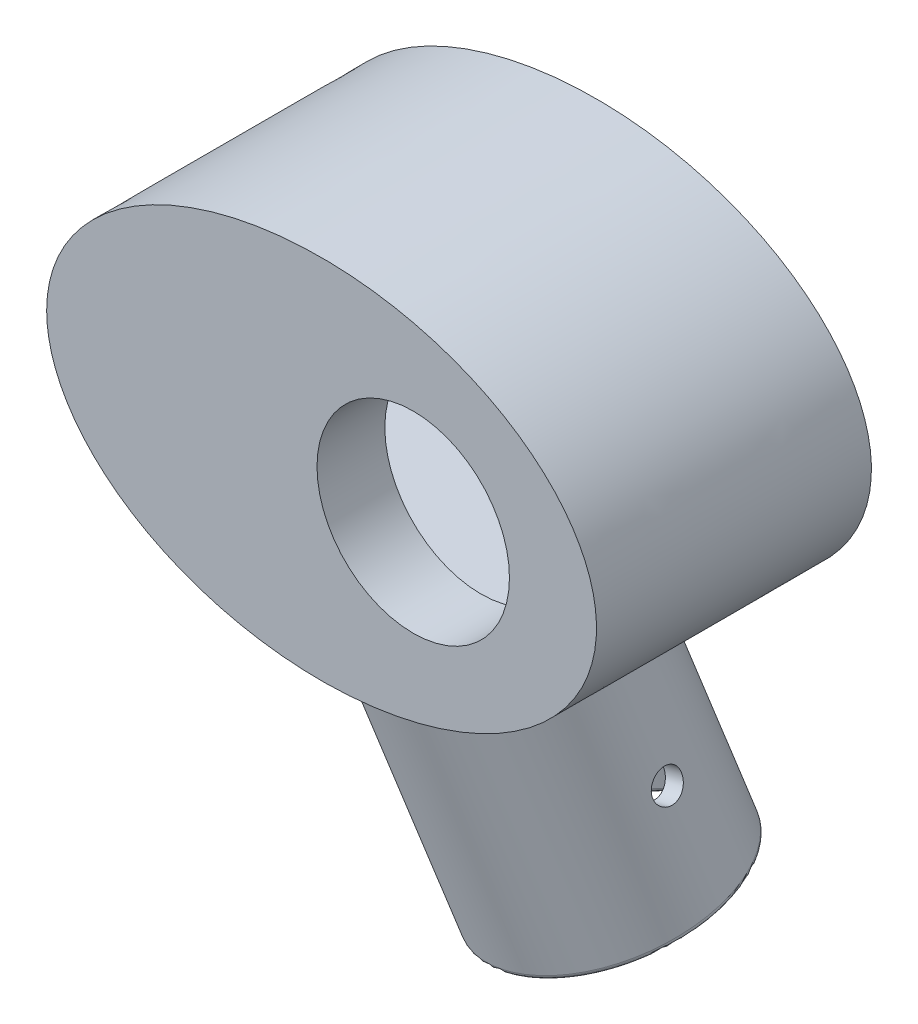
SolidWorks part; units mm, degrees
ref_plane "Front Plane" through (0, 0, 0) normal (0, 0, 1) x (1, 0, 0)
ref_plane "Top Plane" through (0, 0, 0) normal (0, 1, 0) x (1, 0, 0)
ref_plane "Right Plane" through (0, 0, 0) normal (1, 0, 0) x (0, 0, -1)
sketch "Sketch2" plane through (0, 0, 0) normal (0, 0, 1) x (1, 0, 0)
  line L102 (-3.3983, 10.2) -> (7.0395, 10.2) construction
  line L103 (7.0395, 10.2) -> (29.1, 10.2) construction
  line L104 (30.1, 9.2) -> (30.1, 0.75) construction
  line L105 (31.7, 0.75) -> (30.1, 0.75) construction
  line L106 (31.7, 0.75) -> (35.9, 0.75) construction
  line L107 (35.9, 0.75) -> (35.9, -0.75) construction
  line L108 (35.9, -0.75) -> (30.1, -0.75) construction
  line L109 (30.1, -0.75) -> (30.1, -9.2) construction
  line L110 (29.1, -10.2) -> (7.0395, -10.2) construction
  line L111 (7.0395, -10.2) -> (-3.3983, -10.2) construction
  line L112 (-3.3983, -10.2) -> (-9.1, -10.2) construction
  line L113 (-11.7, -0.75) -> (-10.1, -0.75) construction
  line L114 (-11.7, -0.75) -> (-15.9, -0.75) construction
  line L115 (-15.9, -0.75) -> (-15.9, 0.75) construction
  line L116 (-15.9, 0.75) -> (-11.7, 0.75) construction
  line L117 (-10.1, 0.75) -> (-11.7, 0.75) construction
  line L118 (-10.1, -9.2) -> (-10.1, -0.75) construction
  line L119 (-10.1, 0.75) -> (-10.1, 9.2) construction
  line L120 (-9.1, 10.2) -> (-3.3983, 10.2) construction
  line L121 (-3.3983, 10.6) -> (7.0395, 10.6)
  line L122 (7.0395, 10.6) -> (29.1, 10.6)
  line L123 (30.5, 9.2) -> (30.5, 1.15)
  line L124 (31.7, 1.15) -> (30.5, 1.15)
  line L125 (31.7, 1.15) -> (36.3, 1.15)
  line L126 (36.3, 1.15) -> (36.3, -1.15)
  line L127 (36.3, -1.15) -> (30.5, -1.15)
  line L128 (30.5, -1.15) -> (30.5, -9.2)
  line L129 (29.1, -10.6) -> (7.0395, -10.6)
  line L130 (7.0395, -10.6) -> (-3.3983, -10.6)
  line L131 (-3.3983, -10.6) -> (-9.1, -10.6)
  line L132 (-10.5, -9.2) -> (-10.5, -1.15)
  line L133 (-11.7, -1.15) -> (-10.5, -1.15)
  line L134 (-11.7, -1.15) -> (-16.3, -1.15)
  line L135 (-16.3, -1.15) -> (-16.3, 1.15)
  line L136 (-16.3, 1.15) -> (-11.7, 1.15)
  line L137 (-10.5, 1.15) -> (-11.7, 1.15)
  line L138 (-10.5, 1.15) -> (-10.5, 9.2)
  line L139 (-9.1, 10.6) -> (-3.3983, 10.6)
  arc A20 (30.1, 9.2) -> (29.1, 10.2) centre (29.1, 9.2) ccw construction
  arc A21 (29.1, -10.2) -> (30.1, -9.2) centre (29.1, -9.2) ccw construction
  arc A22 (-10.1, -9.2) -> (-9.1, -10.2) centre (-9.1, -9.2) ccw construction
  arc A23 (-9.1, 10.2) -> (-10.1, 9.2) centre (-9.1, 9.2) ccw construction
  arc A24 (30.5, 9.2) -> (29.1, 10.6) centre (29.1, 9.2) ccw
  arc A25 (29.1, -10.6) -> (30.5, -9.2) centre (29.1, -9.2) ccw
  arc A26 (-10.5, -9.2) -> (-9.1, -10.6) centre (-9.1, -9.2) ccw
  arc A27 (-9.1, 10.6) -> (-10.5, 9.2) centre (-9.1, 9.2) ccw
  ellipse E0 centre (10, 0) end of major axis (40, 0) minor radius 20
  dimension "D2" = 60
  dimension "D3" = 40
  dimension "D4" = 10
  dimension "D1" = 0.4
extrude "Boss-Extrude1" add sketch "Sketch2" along normal blind 30 contours E0 region at (-19.2789, -0.0201, 0)
sketch "Sketch3" plane through (0, 0, 0) normal (0, 0, -1) x (-1, 0, 0)
  arc A0 (-36.8729, -5.875) -> (-36.8729, -4.125) centre (-34.8, -5) ccw construction
  arc A1 (-36.8729, 4.125) -> (-36.8729, 5.875) centre (-34.8, 5) ccw construction
  arc A2 (16.8729, 5.875) -> (16.8729, 4.125) centre (14.8, 5) ccw construction
  arc A3 (16.8729, -4.125) -> (16.8729, -5.875) centre (14.8, -5) ccw construction
  arc A4 (-36.8729, -5.875) -> (-36.8729, -4.125) centre (-34.8, -5) ccw construction
  arc A5 (-36.8729, 4.125) -> (-36.8729, 5.875) centre (-34.8, 5) ccw construction
  arc A6 (16.8729, 5.875) -> (16.8729, 4.125) centre (14.8, 5) ccw construction
  arc A7 (16.8729, -4.125) -> (16.8729, -5.875) centre (14.8, -5) ccw construction
  arc A8 (16.8729, -5.875) -> (16.8729, -4.125) centre (14.8, -5) ccw construction
  arc A9 (16.8729, 4.125) -> (16.8729, 5.875) centre (14.8, 5) ccw construction
  arc A10 (-36.8729, 5.875) -> (-36.8729, 4.125) centre (-34.8, 5) ccw construction
  arc A11 (-36.8729, -4.125) -> (-36.8729, -5.875) centre (-34.8, -5) ccw construction
  arc A12 (-35.9516, -5.4861) -> (-35.9516, -4.5139) centre (-34.8, -5) ccw
  arc A13 (-35.9516, -4.5139) -> (-35.9516, -5.4861) centre (-34.8, -5) ccw
  arc A14 (-35.9516, 4.5139) -> (-35.9516, 5.4861) centre (-34.8, 5) ccw
  arc A15 (-35.9516, 5.4861) -> (-35.9516, 4.5139) centre (-34.8, 5) ccw
  arc A16 (15.9516, 5.4861) -> (15.9516, 4.5139) centre (14.8, 5) ccw
  arc A17 (15.9516, 4.5139) -> (15.9516, 5.4861) centre (14.8, 5) ccw
  arc A18 (15.9516, -4.5139) -> (15.9516, -5.4861) centre (14.8, -5) ccw
  arc A19 (15.9516, -5.4861) -> (15.9516, -4.5139) centre (14.8, -5) ccw
  dimension "D1" = 1.25
extrude "Cut-Extrude1" cut sketch "Sketch3" against normal blind 3
ref_plane "Plane3" through (10, 0, 0) normal (1, 0, 0) x (0, 0, -1)
sketch "Sketch16" [suppressed] plane through (10, 0, 0) normal (1, 0, 0) x (0, 0, -1)
  line L0 (0, 0) -> (50000, 0) construction
ref_plane "Plane6" [suppressed] through (9.648, 1.8427, 0) normal (-0.9822, -0.1876, 0) x (0, 0, -1)
sketch "Sketch6" plane through (11.1721, -6.137, 0) normal (-0.9822, -0.1876, 0) x (-0.1876, 0.9822, 0)
  line L1 (26.6831, 0) -> (-14.1873, 0) construction
  line L3 (-14.1873, -30) -> (26.6831, -30) construction
  line L7 (26.6831, -15) -> (51.6831, -15)
  line L8 (26.6831, 0) -> (-14.1873, 0) construction
  line L9 (-14.1873, -30) -> (26.6831, -30) construction
  line L10 (26.6831, 0) -> (26.6831, -30) construction
  dimension "D1" = 25
ref_plane "Plane1" through (1.4762, 44.6285, 15) normal (-0.1876, 0.9822, 0) x (0.9822, 0.1876, 0)
sketch "Sketch7" plane through (1.4762, 44.6285, 15) normal (-0.1876, 0.9822, 0) x (0.9822, 0.1876, 0)
  circle A0 centre (0, 0) radius 10.35
  circle A1 centre (0, 0) radius 12.35
  point P12 (0, 0)
  dimension "D1" = 20.7
  dimension "D2" = 2
extrude "Boss-Extrude2" [suppressed] add sketch "Sketch7" against normal up to body
sketch "Sketch8" plane through (0, 0, 30) normal (0, 0, 1) x (1, 0, 0)
  line L0 (10, 0) -> (10, -3.4904) construction
  ellipse E0 centre (10, 0) end of major axis (40, 0) minor radius 20 construction
  ellipse E1 centre (10, 0) end of major axis (40, 0) minor radius 20
extrude "Boss-Extrude4" add sketch "Sketch8" against normal up to surface (7.4 mm away)
sketch "Sketch12" [suppressed] plane through (10, -10, 0) normal (-1, 0, 0) x (0, 1, 0)
  line L6 (30, -30) -> (30, 0) construction
  line L7 (30, -15) -> (52.3116, -15) construction
  circle A0 centre (41.1558, -15) radius 1.7
  ellipse E0 centre (54.6285, -15) end of major axis (54.6285, -27.35) minor radius 2.3169 construction
  dimension "D1" = 3.4
extrude "Cut-Extrude3" [suppressed] cut sketch "Sketch12" against normal through all both and the other way through all
sketch "Sketch15" plane through (10, 0, 0) normal (1, 0, 0) x (0, 0, -1)
  line L0 (0, 0) -> (50000, 0) construction
  line L1 (0, -20) -> (0, 20) construction
  point P4 (0, 0)
ref_plane "Plane4" through (9.4211, -2.3354, 0) normal (0.9706, -0.2406, 0) x (0, 0, -1)
sketch "Sketch9" plane through (12.5635, 10.3412, 0) normal (0.9706, -0.2406, 0) x (-0.2406, -0.9706, 0)
  line L0 (31.3652, -30) -> (31.3652, 0) construction
  line L1 (31.3652, -30) -> (31.3652, 0) construction
  line L2 (31.3652, -15) -> (55.6745, -9.1639)
  dimension "D1" = 25
  dimension "D2" = 13.5
ref_plane "Plane2" through (-0.8323, -43.6977, 9.1639) normal (-0.234, -0.9438, -0.2334) x (-0.4258, 0.3153, -0.8481)
sketch "Sketch10" plane through (-0.8323, -43.6977, 9.1639) normal (-0.234, -0.9438, -0.2334) x (-0.4258, 0.3153, -0.8481)
  line L0 (-12.7213, -7.1349) -> (12.7213, 7.1349) construction
  circle A0 centre (0, 0) radius 10.35
  circle A1 centre (0, 0) radius 12.35
  dimension "D1" = 20.7
  dimension "D2" = 2
extrude "Boss-Extrude5" add sketch "Sketch10" against normal up to surface (28.1469 mm away) up to face at (40, 0, 30)
sketch "Sketch11" plane through (12.5635, 10.3412, 0) normal (0.9706, -0.2406, 0) x (-0.2406, -0.9706, 0)
  line L2 (31.3652, 0) -> (31.3652, -30) construction
  line L3 (31.3652, -15) -> (55.6745, -9.1639) construction
  line L4 (58.0906, -19.2279) -> (53.2583, 0.9002) construction
  circle A1 centre (43.5198, -12.0819) radius 1.7
  dimension "D1" = 3.4
extrude "Cut-Extrude2" cut sketch "Sketch11" against normal through all both and the other way through all
sketch "Sketch13" plane through (0, 0, 30) normal (0, 0, 1) x (1, 0, 0)
  circle A0 centre (0, 0) radius 10.5
  dimension "D1" = 21
extrude "Cut-Extrude4" cut sketch "Sketch13" against normal through all both and the other way through all
sketch "Sketch14" plane through (0, 0, 30) normal (0, 0, 1) x (1, 0, 0)
  circle A1 centre (20, 0) radius 4
  ellipse E3 centre (10, 0) end of major axis (40, 0) minor radius 20
  ellipse E4 centre (10, 0) end of major axis (40, 0) minor radius 20
  dimension "D1" = 8
  dimension "D3" = 10
  dimension "D2" = 0
extrude "Cut-Extrude5" [suppressed] cut sketch "Sketch14" against normal through all both and the other way through all contours A1
ref_plane "Plane5" through (-25, 0, 0) normal (1, 0, 0) x (0, 0, -1)
mirror "Mirror1" about plane through (-25, 0, 0) normal (1, 0, 0) of bodies 112 113
delete or keep bodies "Body-Delete/Keep 1" type delete bodies bodies 112
fillet "Fillet1" [suppressed] radius 0.5
fillet "Fillet2" radius 0.5 2 edges at (-61.1549, -46.6692, 9.1639) (-59.2136, -46.188, 9.1639)
fillet "Fillet3" [suppressed] radius 0.5
fillet "Fillet4" [suppressed] radius 0.5
